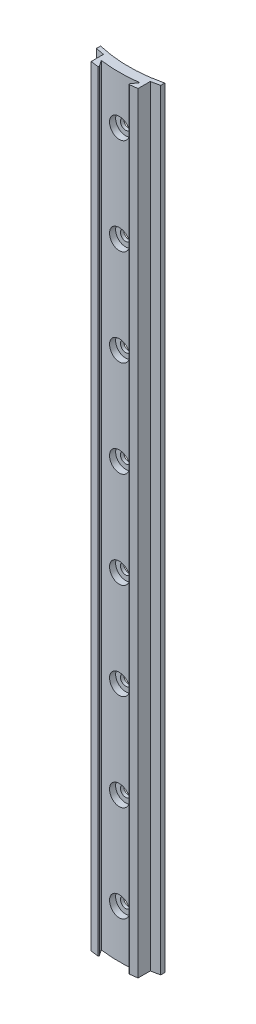
SolidWorks part; units mm, degrees
ref_plane "Front" through (0, 0, 0) normal (0, 0, 1) x (1, 0, 0)
ref_plane "Top" through (0, 0, 0) normal (0, 1, 0) x (1, 0, 0)
ref_plane "Right" through (0, 0, 0) normal (1, 0, 0) x (0, 0, -1)
ref_plane "Plane1" through (0, 15, 0) normal (0, 1, 0) x (1, 0, 0)
sketch "Sketch1" plane through (0, 0, 0) normal (0, 1, 0) x (1, 0, 0)
  line L1 (0, 0) -> (0, -68.2294) construction
  line L2 (-10, -44.3875) -> (-10, -41.3068)
  line L3 (10, -44.3875) -> (10, -41.3068)
  line L4 (-10, -41.3068) -> (10, -44.3875) construction
  line L5 (10, -41.3068) -> (-10, -44.3875) construction
  arc A1 (-10, -41.3068) -> (10, -41.3068) centre (0, 0) ccw
  arc A2 (-10, -44.3875) -> (10, -44.3875) centre (0, 0) ccw
  point P0 (0, -42.5)
  point P3 (0, -42.8471)
  point P7 (0, -45.5)
  dimension "D1" = 42.5
  dimension "D2" = 3
  dimension "D3" = 20
sketch "Sketch2" plane through (0, 15, 0) normal (0, 1, 0) x (1, 0, 0)
  line L0 (-10, -44.3875) -> (-10, -41.3068) construction
  line L1 (10, -44.3875) -> (10, -41.3068) construction
  line L2 (-10, -44.3875) -> (-10, -41.3068)
  line L3 (10, -44.3875) -> (10, -41.3068)
  arc A0 (-10, -41.3068) -> (10, -41.3068) centre (0, 0) ccw construction
  arc A1 (-10, -44.3875) -> (10, -44.3875) centre (0, 0) ccw construction
  arc A2 (-10, -41.3068) -> (10, -41.3068) centre (0, 0) ccw
  arc A3 (-10, -44.3875) -> (10, -44.3875) centre (0, 0) ccw
extrude "Boss-Extrude1" add sketch "Sketch2" along normal blind 240
ref_plane "Plane2" through (0, 0, 45.5) normal (0, 0, 1) x (1, 0, 0)
sketch "Sketch3" plane through (0, 0, 45.5) normal (0, 0, 1) x (1, 0, 0)
  line L0 (0, 0) -> (0, 367.1758) construction
  line L1 (0, 30) -> (0, 60) construction
  line L2 (-10, 15) -> (10, 15) construction
  line L3 (10, 255) -> (-10, 255) construction
  circle A1 centre (0, 30) radius 1.625
  circle A2 centre (0, 30) radius 3.125
  circle A3 centre (0, 60) radius 3.125
  circle A4 centre (0, 60) radius 1.625
  circle A5 centre (0, 90) radius 3.125
  circle A6 centre (0, 90) radius 1.625
  circle A7 centre (0, 120) radius 3.125
  circle A8 centre (0, 120) radius 1.625
  circle A9 centre (0, 150) radius 3.125
  circle A10 centre (0, 150) radius 1.625
  circle A11 centre (0, 180) radius 3.125
  circle A12 centre (0, 180) radius 1.625
  circle A13 centre (0, 210) radius 3.125
  circle A14 centre (0, 210) radius 1.625
  circle A15 centre (0, 240) radius 3.125
  circle A16 centre (0, 240) radius 1.625
  dimension "D1" = 6.25
  dimension "D5" = 3.25
  dimension "D4" = 15
  dimension "D3" = 30
  dimension "D2" = 8
sketch "Sketch5" plane through (0, 255, 0) normal (0, 1, 0) x (1, 0, 0)
  line L2 (-8, -41.3068) -> (-8, -44.3875)
  line L3 (-8, -42.9912) -> (-8, -44.7912)
  line L4 (10, -44.3875) -> (10, -41.3068) construction
  line L5 (8, -44.3875) -> (8, -41.3068)
  line L6 (8, -44.7912) -> (8, -42.9912)
  line L7 (-10, -41.3068) -> (-10, -44.3875) construction
  line L8 (10, -44.3875) -> (10, -42.5704)
  line L9 (-10, -42.5704) -> (-10, -44.3875)
  arc A1 (-10, -44.3875) -> (10, -44.3875) centre (0, 0) ccw construction
  arc A2 (-10, -44.3875) -> (-8, -44.7912) centre (0, 0) ccw
  arc A4 (8, -44.7912) -> (10, -44.3875) centre (0, 0) ccw
  arc A5 (8, -42.9912) -> (10, -42.5704) centre (0, 0) ccw
  arc A6 (-10, -42.5704) -> (-8, -42.9912) centre (0, 0) ccw
  dimension "D3" = 1.8
  dimension "D1" = 2
  dimension "D2" = 2
extrude "Cut-Extrude3" cut sketch "Sketch5" against normal through all
sketch "Sketch6" plane through (0, 255, 0) normal (0, 1, 0) x (1, 0, 0)
  line L0 (-8, -44.7912) -> (-8, -46.8215)
  line L1 (8, -44.7912) -> (8, -46.8215)
  line L2 (-6, -45.1027) -> (-4.7439, -46.9314)
  line L3 (6, -45.1027) -> (4.7439, -46.9314)
  arc A1 (-8, -44.7912) -> (8, -44.7912) centre (0, 0) ccw construction
  arc A2 (-8.3516, -46.76) -> (8.3516, -46.76) centre (0, 0) ccw
  arc A3 (-8, -46.8215) -> (-4.9295, -47.2435) centre (0, 0) ccw
  arc A4 (-8, -44.7912) -> (-6, -45.1027) centre (0, 0) ccw
  arc A5 (6, -45.1027) -> (8, -44.7912) centre (0, 0) ccw
  arc A6 (4.9295, -47.2435) -> (8, -46.8215) centre (0, 0) ccw
  arc A7 (4.7439, -46.9314) -> (4.9295, -47.2435) centre (4.9087, -47.0446) ccw
  arc A8 (-4.7439, -46.9314) -> (-4.9295, -47.2435) centre (-4.9087, -47.0446) cw
  point P16 (4.5, -47.2864)
  point P19 (-4.5, -47.2864)
  dimension "D6" = 0.2
  dimension "D2" = 2
  dimension "D3" = 3.5
  dimension "D4" = 2
  dimension "D5" = 3.5
  dimension "D1" = 2
extrude "Boss-Extrude2" add sketch "Sketch6" against normal through all
extrude "Cut-Extrude4" cut sketch "Sketch3" against normal blind 270 contours A16 | A14 | A12 | A10 | A8 | A6 | A4 | A1
extrude "Cut-Extrude5" cut sketch "Sketch3<5>" against normal blind 2
sketch "Sketch3<5>" plane through (0, 0, 45.5) normal (0, 0, 1) x (1, 0, 0) same geometry as "Sketch3"
sketch "Sketch7" plane through (0, 15, 0) normal (0, -1, 0) x (1, 0, 0)
  line L0 (-3.6476, 41.5) -> (3.6286, 41.5) construction
  dimension "D1" = 1
sketch "Sketch8" plane through (0, 255, 0) normal (0, 1, 0) x (1, 0, 0)
  line L2 (-7.3, -46.8215) -> (-7.3, -42.9912)
  line L3 (-7.3, -48.9743) -> (-7.3, -43.1156)
  line L4 (-10, -42.5704) -> (-7.3, -48.9743)
  line L5 (7.3, -42.9912) -> (7.3, -46.8215)
  line L6 (7.3, -43.1156) -> (7.3, -48.9743)
  line L8 (10, -42.5704) -> (7.3, -48.9743)
  arc A0 (-10, -42.5704) -> (-8, -42.9912) centre (0, 0) ccw construction
  arc A1 (-10, -42.5704) -> (-7.3, -43.1156) centre (0, 0) ccw
  arc A2 (8, -42.9912) -> (10, -42.5704) centre (0, 0) ccw construction
  arc A3 (7.3, -43.1156) -> (10, -42.5704) centre (0, 0) ccw
  point P12 (0, 0)
  dimension "D1" = 0.7
  dimension "D2" = 0.7
extrude "Cut-Extrude6" cut sketch "Sketch8" against normal through all contours L3 A1 L4 | L6 L8 A3
